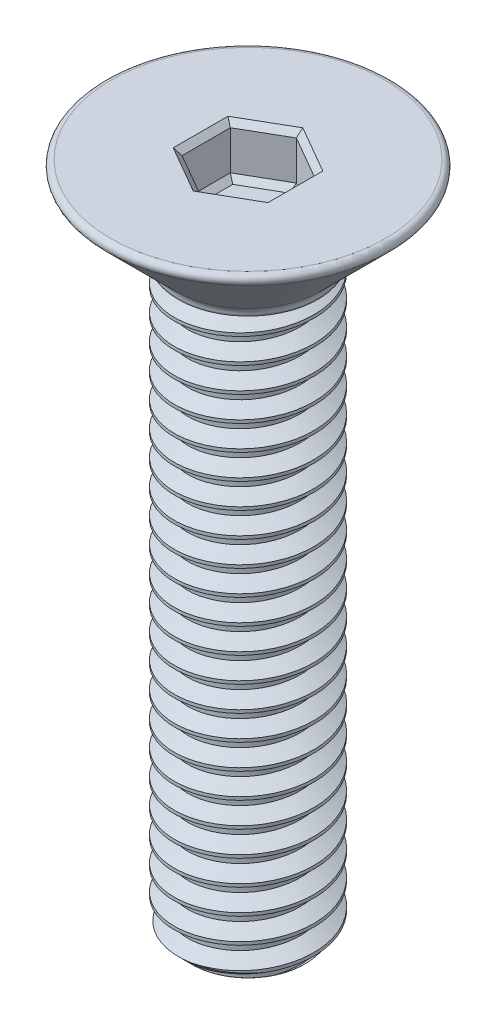
SolidWorks part; units mm, degrees
material "AISI Type A2 Tool Steel"
ref_plane "Front Plane" through (0, 0, 0) normal (0, 0, 1) x (1, 0, 0)
ref_plane "Top Plane" through (0, 0, 0) normal (0, 1, 0) x (1, 0, 0)
ref_plane "Right Plane" through (0, 0, 0) normal (1, 0, 0) x (0, 0, -1)
sketch "Sketch1" plane through (0, 0, 0) normal (0, 1, 0) x (1, 0, 0)
  circle A0 centre (0, 0) radius 1.25
  dimension "D1" = 2.5
extrude "Boss-Extrude1" add sketch "Sketch1" along normal blind 10.45
thread "Thread1" pitch 0.45 method cut profile "Thread Profile1" start angle 0, offset 1, length 0, pitch 0.45, diameter 2.5
ref_plane "Plane1" through (1.25, -1, 0) normal (0, 0, 1) x (1, 0, 0)
sketch "Thread Profile1" plane through (1.25, -1, 0) normal (0, 0, 1) x (1, 0, 0)
  line L0 (0, 0) -> (0, 0.45) construction
  line L11 (0, 0) -> (0, 0.3937)
  line L12 (0, 0.3937) -> (-0.2436, 0.2531)
  line L13 (-0.2436, 0.2531) -> (-0.2436, 0.1406)
  line L15 (-0.2436, 0.1406) -> (0, 0)
  line L17 (-0.2436, 0.1969) -> (0, 0.1969) construction
  point P2 (0, 0)
  dimension "Pitch" = 0.45
  dimension "Profile_Angle" = 60
  dimension "Profile_Land" = 0.1125
  dimension "Profile_Height" = 0.2436
sketch "Sketch5" plane through (0, 10.45, 0) normal (0, 1, 0) x (1, 0, 0)
  circle A0 centre (0, 0) radius 1.25
  dimension "D1" = 2.5
extrude "Boss-Extrude2" add sketch "Sketch5" along normal blind 0.1
sketch "Sketch6" plane through (0, 10.55, 0) normal (0, 1, 0) x (1, 0, 0)
  circle A0 centre (0, 0) radius 1.25
  dimension "D1" = 2.5
extrude "Boss-Extrude3" add sketch "Sketch6" along normal blind 1.45 draft 45 draft outward yes
fillet "Fillet1" radius 0.2 1 edges at (0, 10.55, 1.25)
fillet "Fillet2" radius 0.1 1 edges at (0, 12, 2.7)
sketch "Sketch7" plane through (0, 0, 0) normal (0, 0, 1) x (1, 0, 0)
  line L0 (0, 0) -> (0, 0.3237) construction
  line L1 (0, 0) -> (1.26, 0) construction
  line L2 (1.26, 0) -> (1.26, 0.26)
  line L3 (1.26, 0.26) -> (1, 0)
  line L4 (1, 0) -> (1.26, 0)
  dimension "D1" = 45
  dimension "D2" = 0.26
  dimension "D3" = 1.26
revolve "Cut-Revolve1" cut sketch "Sketch7" angle 360 about L0
sketch "Sketch8" plane through (0, 12, 0) normal (0, 1, 0) x (1, 0, 0)
  line L1 (0, 0.866) -> (-0.75, 0.433)
  line L2 (-0.75, 0.433) -> (-0.75, -0.433)
  line L3 (-0.75, -0.433) -> (0, -0.866)
  line L4 (0, -0.866) -> (0.75, -0.433)
  line L5 (0.75, -0.433) -> (0.75, 0.433)
  line L6 (0.75, 0.433) -> (0, 0.866)
  circle A0 centre (0, 0) radius 0.75 construction
  dimension "D1" = 1.5
extrude "Cut-Extrude1" cut sketch "Sketch8" against normal blind 0.8
chamfer "Chamfer1" distance 0.1 angle 45 6 edges at (-0.75, 12, 0) (-0.375, 12, 0.6495) (0.375, 12, 0.6495) (0.75, 12, 0) (0.375, 12, -0.6495) (-0.375, 12, -0.6495)
sketch "Sketch9" plane through (0, 11.2, 0) normal (0, 1, 0) x (1, 0, 0)
  line L1 (0, 0.866) -> (-0.75, 0.433)
  line L2 (-0.75, 0.433) -> (-0.75, -0.433)
  line L3 (-0.75, -0.433) -> (0, -0.866)
  line L4 (0, -0.866) -> (0.75, -0.433)
  line L5 (0.75, -0.433) -> (0.75, 0.433)
  line L6 (0.75, 0.433) -> (0, 0.866)
  circle A0 centre (0, 0) radius 0.75 construction
extrude "Cut-Extrude2" cut sketch "Sketch9" against normal blind 0.1 draft 45
